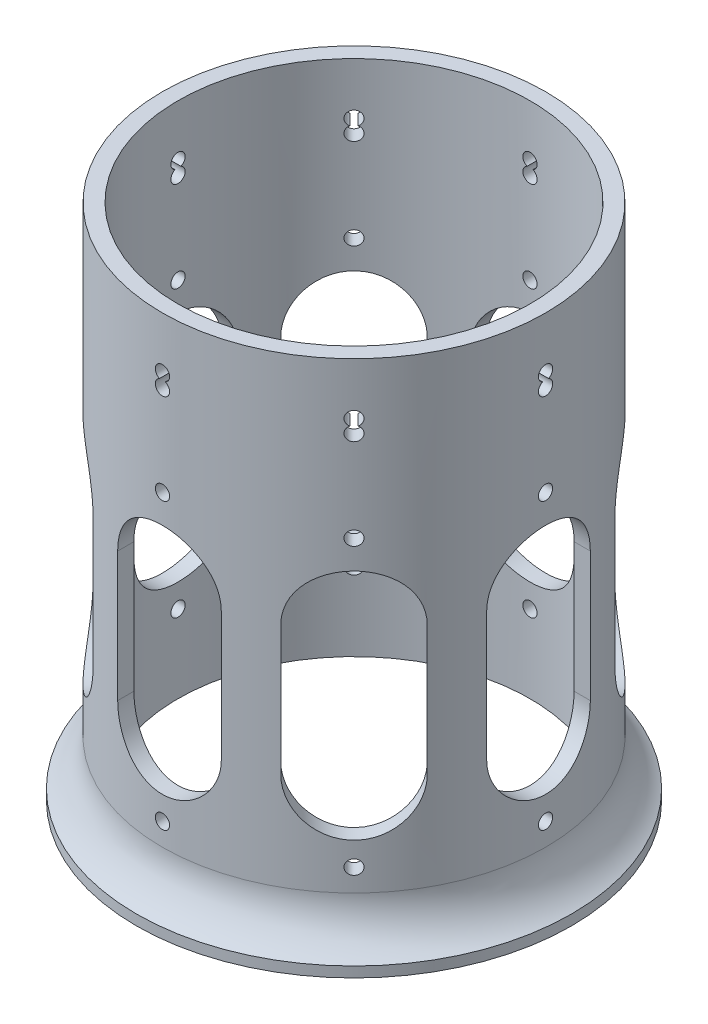
SolidWorks part; units mm, degrees
ref_plane "Front Plane" through (0, 0, 0) normal (0, 0, 1) x (1, 0, 0)
ref_plane "Top Plane" through (0, 0, 0) normal (0, 1, 0) x (1, 0, 0)
ref_plane "Right Plane" through (0, 0, 0) normal (1, 0, 0) x (0, 0, -1)
sketch "Body tube profile" plane through (0, 0, 0) normal (0, 1, 0) x (1, 0, 0)
  circle A0 centre (0, 0) radius 34
  dimension "D1" = 68
sketch "Sketch2" plane through (0, 0, 0) normal (0, 1, 0) x (1, 0, 0)
  circle A0 centre (0, 0) radius 34 construction
  circle A1 centre (0, 0) radius 34
  circle A2 centre (0, 0) radius 37
  dimension "D1" = 3
extrude "Main extrude" add sketch "Sketch2" along normal blind 100
sketch "Sketch3" plane through (0, 0, 0) normal (0, 0, 1) x (1, 0, 0)
  line L0 (-37, 0) -> (37, 0) construction
  line L1 (37, 100) -> (-37, 100) construction
  line L2 (34, 100) -> (-34, 100) construction
  circle A0 centre (0, 15) radius 1.375
  arc A1 (-0.5728, 88.75) -> (0.5728, 88.75) centre (0, 87.5) ccw
  circle A2 centre (0, 70) radius 1.375
  arc A3 (0.5728, 88.75) -> (-0.5728, 88.75) centre (0, 90) ccw
  point P11 (0, 0)
  point P14 (0, 0)
  dimension "D1" = 2.75
  dimension "D3" = 2.75
  dimension "D2" = 15
  dimension "D4" = 12.5
  dimension "D5" = 10
  dimension "D6" = 30
extrude "Screwhole" cut sketch "Sketch3" along normal blind 100
sketch "Sketch4" plane through (0, 0, 0) normal (0, 0, 1) x (1, 0, 0)
  line L0 (0, 54.5) -> (0, 29.5) construction
  line L1 (10, 54.5) -> (10, 29.5)
  line L2 (-10, 54.5) -> (-10, 29.5)
  arc A0 (10, 54.5) -> (-10, 54.5) centre (0, 54.5) ccw
  arc A1 (-10, 29.5) -> (10, 29.5) centre (0, 29.5) ccw
  point P3 (0, 42)
  dimension "D3" = 10
  dimension "D1" = 42
  dimension "D2" = 25
extrude "Weight reduction" cut sketch "Sketch4" along normal blind 100
pattern_circular "Screwhole pattern" count 8 over 360 about axis through (0, 0, 0) along (0, 1, 0) of "Screwhole", "Weight reduction"
sketch "Sketch5" plane through (0, 0, 0) normal (0, -1, 0) x (1, 0, 0)
  circle A1 centre (0, 0) radius 37
  circle A2 centre (0, 0) radius 37 construction
  circle A3 centre (0, 0) radius 34 construction
  circle A27 centre (0, 0) radius 42
  circle A40 centre (0, 0) radius 34
  point P63 (0, 0)
  dimension "D1" = 0
  dimension "D7" = 5
extrude "Plate for better adhesion" add sketch "Sketch5" against normal blind 2
fillet "Fillet1" radius 10 1 edges at (0, 2, -37)
